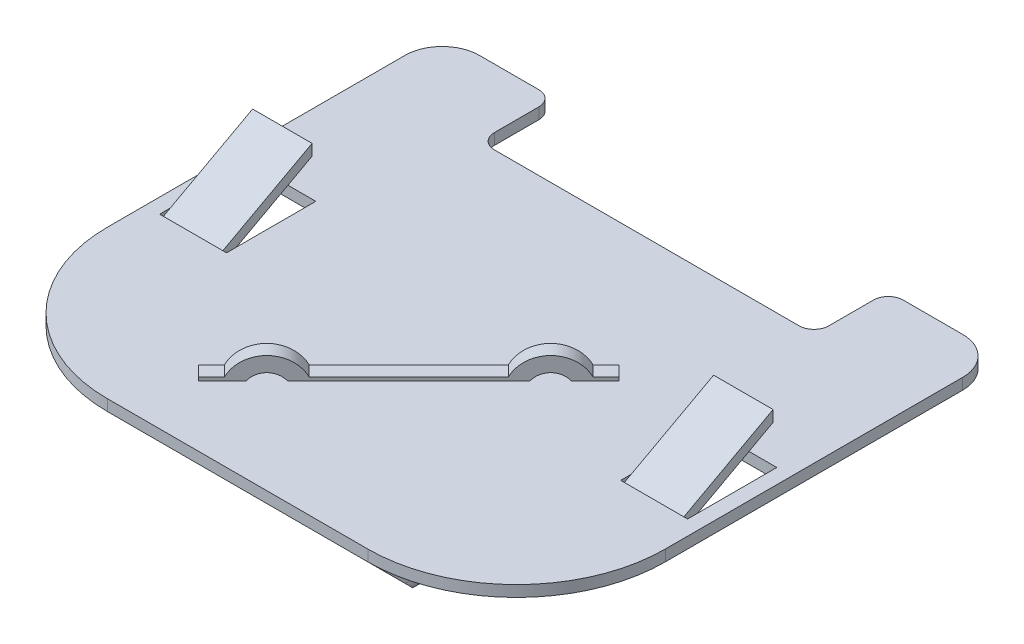
SolidWorks part; units mm, degrees
material "Plain Carbon Steel"
ref_plane "Front Plane" through (0, 0, 0) normal (0, 0, 1) x (1, 0, 0)
ref_plane "Top Plane" through (0, 0, 0) normal (0, 1, 0) x (1, 0, 0)
ref_plane "Right Plane" through (0, 0, 0) normal (1, 0, 0) x (0, 0, -1)
sketch "Sketch1" plane through (0, 0, 0) normal (0, 1, 0) x (1, 0, 0)
  line L1 (-7.5, 6.5) -> (7.5, 6.5)
  line L2 (-7.5, 6.5) -> (-7.5, -6.5)
  line L3 (-7.5, -6.5) -> (7.5, -6.5)
  line L4 (7.5, 6.5) -> (7.5, -6.5)
  line L5 (-7.5, 6.5) -> (7.5, -6.5) construction
  line L6 (-7.5, -6.5) -> (7.5, 6.5) construction
  point P0 (0, 0)
  dimension "D1" = 15
  dimension "D2" = 13
extrude "BASE" add sketch "Sketch1" along normal blind 0.3
sketch "BATTERY TERMINAL SPRING LOCATION" plane through (0, 0, 0) normal (0, 1, 0) x (1, 0, 0)
  line L0 (2.9698, 1.0698) -> (-2.9698, -4.8698) construction
  line L1 (0, -6.5) -> (0, -1.9) construction
  line L2 (-7.5, -6.5) -> (7.5, -6.5) construction
  dimension "D1" = 8.4
  dimension "D2" = 45
  dimension "D3" = 4.6
ref_axis "BTSL AXIS" through (0, 0, 1.9) along (0, 1, 0)
sketch "Sketch7" plane through (0, 0.3, 0) normal (0, 1, 0) x (1, 0, 0)
  line L1 (7.1, -1.5) -> (5.3, -1.5)
  line L2 (7.1, -1.5) -> (7.1, 0.9)
  line L3 (7.1, 0.9) -> (5.3, 0.9)
  line L4 (5.3, -1.5) -> (5.3, 0.9)
  line L5 (7.1, -1.5) -> (5.3, 0.9) construction
  line L6 (7.1, 0.9) -> (5.3, -1.5) construction
  line L7 (-7.5, -6.5) -> (7.5, -6.5) construction
  line L8 (7.5, -6.5) -> (7.5, 6.5) construction
  dimension "D1" = 1.8
  dimension "D2" = 0.4
  dimension "D3" = 5
  dimension "D4" = 2.4
extrude "LOCKING CLAMP CUT" cut sketch "Sketch7" against normal through all
ref_plane "LCC REFERENCE PLANE" through (6.2, 0, 0) normal (-1, 0, 0) x (0, 0, 1)
sketch "Sketch9" plane through (6.2, 0, 0) normal (-1, 0, 0) x (0, 0, 1)
  line L0 (1.5, 0.3) -> (-0.9, 1.6)
  line L1 (-0.9, 1.6) -> (-0.9, 1.3)
  line L2 (-0.9, 1.3) -> (1.5, 0)
  line L3 (1.5, 0) -> (1.5, 0.3)
  line L5 (-6.5, 0) -> (6.5, 0) construction
  line L6 (-0.9, 0) -> (-0.9, 0.3) construction
  dimension "D1" = 1.6
extrude "LOCKING CLAMP" add sketch "Sketch9" along normal mid plane 1.6
mirror "LC M" about plane through (0, 0, 0) normal (1, 0, 0) of "LOCKING CLAMP CUT", "LOCKING CLAMP"
ref_plane "SC RP" through (0.95, 0, 0.95) normal (-0.7071, 0, -0.7071) x (-0.7071, 0, 0.7071)
sketch "Sketch11" plane through (0.95, 0, 0.95) normal (-0.7071, 0, -0.7071) x (-0.7071, 0, 0.7071)
  line L0 (4.0435, 0) -> (-1.3565, 0) construction
  line L1 (5.3435, 0) -> (4.6351, 0)
  line L2 (3.4519, 0) -> (-0.7649, 0)
  line L3 (-2.6565, 0) -> (-1.9481, 0)
  arc A0 (4.5365, 0.0833) -> (3.5505, 0.0833) centre (4.0435, 0) ccw
  arc A1 (-0.8635, 0.0833) -> (-1.8495, 0.0833) centre (-1.3565, 0) ccw
  arc A2 (-1.9481, 0) -> (-1.8495, 0.0833) centre (-1.9481, 0.1) ccw
  arc A3 (-0.8635, 0.0833) -> (-0.7649, 0) centre (-0.7649, 0.1) ccw
  arc A4 (3.4519, 0) -> (3.5505, 0.0833) centre (3.4519, 0.1) ccw
  arc A5 (4.6351, 0) -> (4.5365, 0.0833) centre (4.6351, 0.1) cw
  point P13 (-1.8565, 0)
  point P16 (-0.8565, 0)
  point P19 (3.5435, 0)
  point P22 (4.5435, 0)
  dimension "D2" = 1
  dimension "D3" = 0.1
  dimension "D1" = 5.4
  dimension "D4" = 8
extrude "SPRING CLASP" add sketch "Sketch11" along normal mid plane 0.4 thin thin type one direction reverse wall 0.4
sketch "Sketch13" plane through (0, 0, 0) normal (1, 0, 0) x (0, 0, -1)
  line L0 (-6.5, 0) -> (-2.5, -4)
  line L1 (-6.5, 0) -> (-6.2, 0)
  line L2 (-6.2, 0) -> (-2.2, -4)
  line L3 (-2.2, -4) -> (-2.5, -4)
  line L4 (-6.5, 0.3) -> (-6.5, 0) construction
  dimension "D1" = 4
  dimension "D2" = 0.3
  dimension "D3" = 45
extrude "WIRE CONNECTION" add sketch "Sketch13" along normal mid plane 2
sketch "Sketch14" plane through (0, 0.3, 0) normal (0, 1, 0) x (1, 0, 0)
  line L0 (7.5, 6.5) -> (-7.5, 6.5) construction
  line L1 (4.5, 4.5) -> (-4.5, 4.5)
  line L2 (4.5, 4.5) -> (4.5, 6.5)
  line L3 (4.5, 6.5) -> (-4.5, 6.5)
  line L4 (-4.5, 4.5) -> (-4.5, 6.5)
  line L5 (4.5, 4.5) -> (-4.5, 6.5) construction
  line L6 (4.5, 6.5) -> (-4.5, 4.5) construction
  line L7 (0, 0) -> (0, 5.5) construction
  point P0 (0, 5.5)
  dimension "D1" = 9
  dimension "D2" = 2
extrude "BOTTOM SLOT CUT" cut sketch "Sketch14" against normal through all
fillet "TS F" radius 1 2 edges at (-7.5, 0.15, -6.5) (7.5, 0.15, -6.5)
fillet "BS F" radius 4 2 edges at (7.5, 0.15, 6.5) (-7.5, 0.15, 6.5)
fillet "WC F" radius 0.5 2 edges at (-1, -4, 2.35) (1, -4, 2.35)
fillet "BSC F" radius 0.4 4 edges at (-4.5, 0.15, -6.5) (-4.5, 0.15, -4.5) (4.5, 0.15, -4.5) (4.5, 0.15, -6.5)
